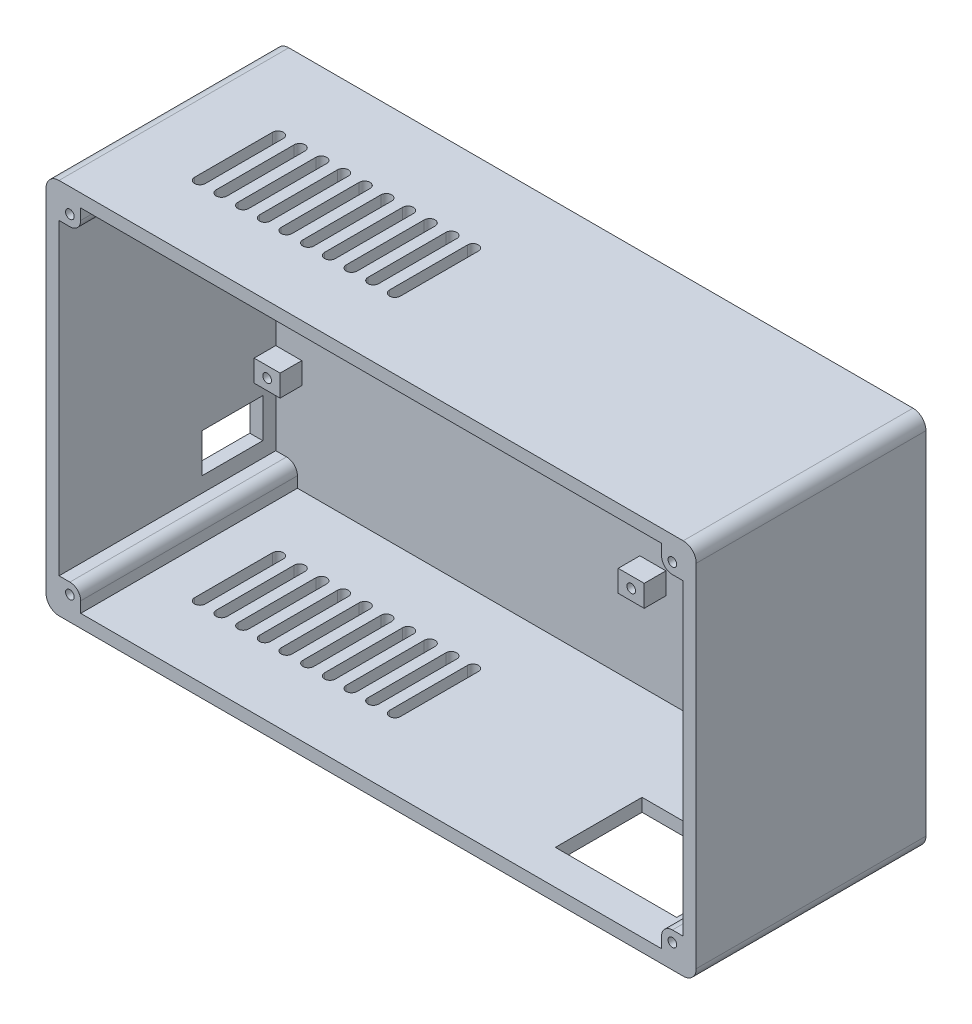
SolidWorks part; units mm, degrees
ref_plane "Front Plane" through (0, 0, 0) normal (0, 0, 1) x (1, 0, 0)
ref_plane "Top Plane" through (0, 0, 0) normal (0, 1, 0) x (1, 0, 0)
ref_plane "Right Plane" through (0, 0, 0) normal (1, 0, 0) x (0, 0, -1)
sketch "Sketch1" plane through (0, 0, 0) normal (0, 0, 1) x (1, 0, 0)
  line L1 (0, 0) -> (150, 0)
  line L2 (0, 0) -> (0, 87)
  line L3 (0, 87) -> (150, 87)
  line L4 (150, 0) -> (150, 87)
  dimension "D1" = 150
  dimension "D2" = 87
extrude "Body_frame" add sketch "Sketch1" along normal blind 53
fillet "body_edges" radius 3 4 edges at (150, 0, 26.5) (150, 87, 26.5) (0, 0, 26.5) (0, 87, 26.5)
shell "Shell1" thickness 3 removed face at (75, 43.5, 53)
sketch "Sketch3" plane through (0, 0, 3) normal (0, 0, 1) x (1, 0, 0)
  line L0 (3, 81.5) -> (8, 81.5) construction
  line L1 (3, 84) -> (8, 84)
  line L2 (3, 84) -> (3, 79)
  line L3 (3, 79) -> (5.5, 79)
  line L4 (8, 84) -> (8, 81.5)
  line L5 (5.5, 84) -> (5.5, 79) construction
  circle A0 centre (5.5, 81.5) radius 1
  arc A1 (8, 81.5) -> (5.5, 79) centre (5.5, 81.5) cw
  dimension "D3" = 2
extrude "screw_hole" add sketch "Sketch3" along normal blind 50
ref_plane "Plane5" through (75, 0, 0) normal (-1, 0, 0) x (0, 0, 1)
ref_plane "Plane6" through (0, 43.5, 0) normal (0, 1, 0) x (1, 0, 0)
mirror "Mirror1" about plane through (75, 0, 0) normal (-1, 0, 0) of "screw_hole"
mirror "Mirror2" about plane through (0, 43.5, 0) normal (0, 1, 0) of "Mirror1", "screw_hole"
sketch "Sketch4" plane through (0, 0, 3) normal (0, 0, 1) x (1, 0, 0)
  line L0 (3, 79) -> (147, 79) construction
  line L1 (3, 74) -> (147, 74) construction
  line L2 (3, 79) -> (3, 8) construction
  line L3 (147, 8) -> (147, 79) construction
  line L4 (3, 24) -> (147, 24) construction
  line L5 (3, 79) -> (3, 8) construction
  line L6 (3, 29) -> (147, 29) construction
  line L7 (147, 8) -> (147, 79) construction
  line L8 (9, 84) -> (9, 24) construction
  line L9 (142, 84) -> (8, 84) construction
  line L10 (93, 79) -> (93, 24) construction
  line L11 (3, 79) -> (93, 79) construction
  line L12 (87, 79) -> (87, 24) construction
  line L13 (3, 76.5) -> (9, 76.5) construction
  line L14 (3, 79) -> (9, 79)
  line L15 (3, 79) -> (3, 74)
  line L16 (3, 74) -> (9, 74)
  line L17 (9, 79) -> (9, 74)
  line L18 (87, 79) -> (93, 79)
  line L19 (87, 79) -> (87, 74)
  line L20 (87, 74) -> (93, 74)
  line L21 (93, 79) -> (93, 74)
  line L22 (3, 29) -> (9, 29)
  line L23 (3, 29) -> (3, 24)
  line L24 (3, 24) -> (9, 24)
  line L25 (9, 29) -> (9, 24)
  line L26 (93, 24) -> (87, 24)
  line L27 (93, 24) -> (93, 29)
  line L28 (93, 29) -> (87, 29)
  line L29 (87, 24) -> (87, 29)
  line L30 (9, 76.5) -> (93, 76.5) construction
  line L31 (3, 26.5) -> (93, 26.5) construction
  line L32 (6, 24) -> (6, 79) construction
  line L33 (90, 79) -> (90, 24) construction
  circle A0 centre (6, 76.5) radius 1
  circle A1 centre (6, 26.5) radius 1
  circle A2 centre (90, 26.5) radius 1
  circle A3 centre (90, 76.5) radius 1
  dimension "D7" = 2
  dimension "D8" = 2
  dimension "D9" = 2
  dimension "D10" = 2
  dimension "D1" = 5
  dimension "D2" = 55
  dimension "D3" = 5
  dimension "D4" = 6
  dimension "D5" = 90
  dimension "D6" = 6
extrude "Boss-Extrude3" add sketch "Sketch4" along normal blind 5
sketch "Sketch5" plane through (3, 0, 0) normal (1, 0, 0) x (0, 0, -1)
  line L0 (-53, 8) -> (-20, 8) construction
  line L1 (0, 3) -> (0, 84) construction
  line L2 (-6, 3) -> (-6, 8) construction
  line L3 (-53, 3) -> (0, 3) construction
  line L4 (-53, 87) -> (0, 87) construction
  line L5 (-51.9185, 20.5) -> (-20, 20.5) construction
  line L6 (-20, 11.5) -> (-6, 11.5) construction
  line L12 (-6, 20.5) -> (-6, 87) construction
  line L17 (-6, 8) -> (0, 8) construction
  line L18 (-6, 11.5) -> (-20, 11.5)
  line L19 (-6, 11.5) -> (-6, 20.5)
  line L20 (-6, 20.5) -> (-20, 20.5)
  line L21 (-20, 11.5) -> (-20, 20.5)
  dimension "D1" = 6
  dimension "D2" = 12.5
  dimension "D3" = 14
  dimension "D4" = 3.5
  dimension "D5" = 9
extrude "switch" cut sketch "Sketch5" against normal through all
sketch "Sketch6" plane through (0, 0, 0) normal (0, -1, 0) x (1, 0, 0)
  line L0 (147, 25) -> (3, 25) construction
  line L1 (147, 0) -> (147, 53) construction
  line L2 (3, 53) -> (3, 0) construction
  line L3 (109.5, 0) -> (109.5, 53) construction
  line L4 (3, 0) -> (147, 0) construction
  line L5 (3, 53) -> (147, 53) construction
  line L6 (147, 53) -> (147, 0) construction
  line L7 (147, 45) -> (109.5, 45) construction
  line L8 (137.5, 45) -> (137.5, 25) construction
  line L10 (109.5, 45) -> (137.5, 45)
  line L11 (109.5, 45) -> (109.5, 25)
  line L12 (109.5, 25) -> (137.5, 25)
  line L13 (137.5, 45) -> (137.5, 25)
  dimension "D1" = 8
  dimension "D2" = 20
  dimension "D3" = 9.5
  dimension "D4" = 28
extrude "AC_IN" cut sketch "Sketch6" against normal blind 3
sketch "Sketch7" plane through (0, 0, 0) normal (0, -1, 0) x (1, 0, 0)
  line L0 (18, 36.75) -> (18, 18.75)
  line L4 (20.5, 36.75) -> (20.5, 18.75)
  arc A0 (20.5, 36.75) -> (18, 36.75) centre (19.25, 36.75) ccw
  arc A1 (18, 18.75) -> (20.5, 18.75) centre (19.25, 18.75) ccw
extrude "air_vent" cut sketch "Sketch7" against normal through all
pattern_linear "LPattern1" count 10 spacing 5 along (1, 0, 0) of "air_vent"
sketch "Sketch8" plane through (0, 0, 0) normal (-1, 0, 0) x (0, 0, 1)
  line L1 (3.5, 87) -> (3.5, 0) construction
  line L2 (0, 87) -> (53, 87) construction
  line L3 (53, 0) -> (0, 0) construction
  line L4 (18.5, 87) -> (18.5, 52.4394) construction
  line L5 (14.5, 84) -> (14.5, 46.6928) construction
  line L6 (53, 84) -> (0, 84) construction
  line L7 (22.5, 84) -> (22.5, 46.6928) construction
  line L8 (22.5, 79) -> (14.5, 79) construction
  line L9 (22.5, 55.9284) -> (14.5, 55.9284) construction
  line L10 (22.5, 70.5) -> (14.5, 70.5) construction
  line L11 (22.5, 57.5) -> (14.5, 57.5) construction
  line L13 (22.5, 70.5) -> (14.5, 70.5)
  line L14 (22.5, 70.5) -> (22.5, 57.5)
  line L15 (22.5, 57.5) -> (14.5, 57.5)
  line L16 (14.5, 70.5) -> (14.5, 57.5)
  dimension "D1" = 3.5
  dimension "D2" = 15
  dimension "D3" = 4
  dimension "D4" = 4
  dimension "D5" = 5
  dimension "D6" = 8.5
  dimension "D7" = 13
extrude "Program_port" cut sketch "Sketch8" against normal blind 3
